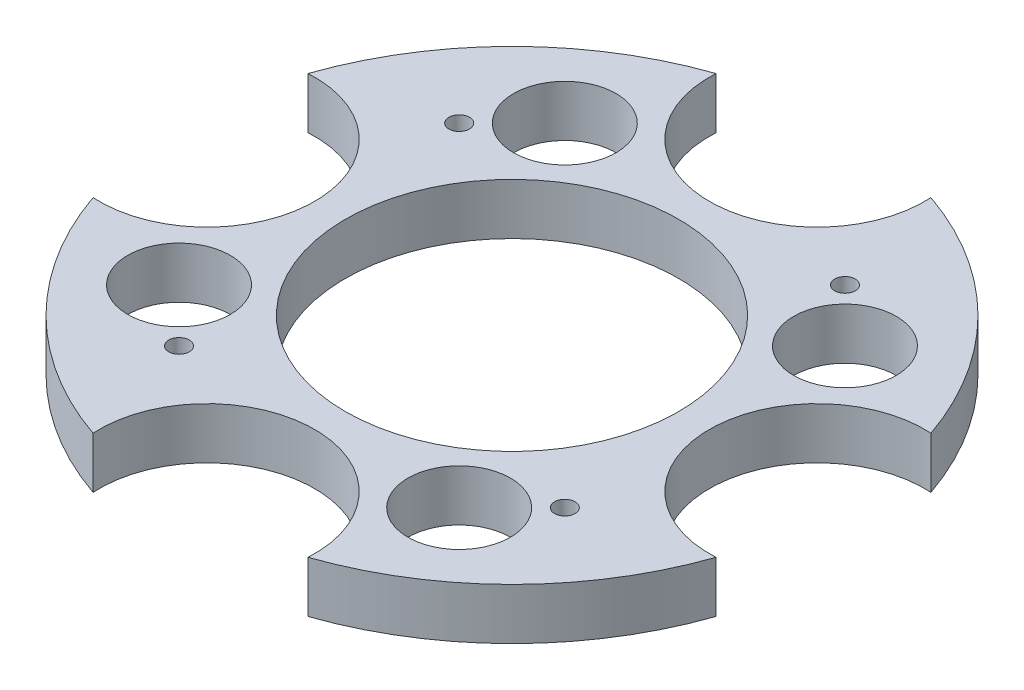
SolidWorks part; units mm, degrees
ref_plane "Front Plane" through (0, 0, 0) normal (0, 0, 1) x (1, 0, 0)
ref_plane "Top Plane" through (0, 0, 0) normal (0, 1, 0) x (1, 0, 0)
ref_plane "Right Plane" through (0, 0, 0) normal (1, 0, 0) x (0, 0, -1)
sketch "Sketch1" plane through (0, 0, 0) normal (0, 1, 0) x (1, 0, 0)
  circle A0 centre (0, 0) radius 32.135
  circle A1 centre (0, 0) radius 16.25
  dimension "D1" = 64.27
  dimension "D2" = 32.5
extrude "Boss-Extrude1" add sketch "Sketch1" along normal mid plane 5
sketch "Sketch2" plane through (0, 2.5, 0) normal (0, 1, 0) x (1, 0, 0)
  line L0 (0, 16.25) -> (0, 19.25) construction
  circle A0 centre (0, 29.75) radius 10.5
  circle A3 centre (0, 0) radius 16.25 construction
  dimension "D1" = 21
  dimension "D2" = 3
extrude "Cut-Extrude1" cut sketch "Sketch2" against normal through all
pattern_circular "CirPattern1" count 4 over 360 about axis through (0, 2.5, 0) along (0, -1, 0) of "Cut-Extrude1" reverse direction yes
sketch "Sketch3" plane through (0, 2.5, 0) normal (0, 1, 0) x (1, 0, 0)
  arc A0 (-10.4812, 30.3777) -> (10.4812, 30.3777) centre (0, 29.75) cw
  arc A1 (-10.4812, 30.3777) -> (10.4812, 30.3777) centre (0, 29.75) ccw construction
  arc A2 (-12.6126, 34.5638) -> (12.6126, 34.5638) centre (0, 29.75) cw
  arc A3 (-12.6126, 34.5638) -> (-19.2914, 25.7002) centre (-31.2979, 41.6953) cw
  arc A4 (-10.4812, 30.3777) -> (-30.3777, 10.4812) centre (0, 0) ccw construction
  arc A5 (-19.2914, 25.7002) -> (-10.4812, 30.3777) centre (0, 0) cw
  arc A6 (10.4812, 30.3777) -> (19.2914, 25.7002) centre (0, 0) cw
  arc A7 (30.3777, 10.4812) -> (10.4812, 30.3777) centre (0, 0) ccw construction
  arc A8 (19.2914, 25.7002) -> (12.6126, 34.5638) centre (31.2979, 41.6953) cw
  point P23 (-18.3629, 26.3716)
  dimension "D1" = 3
  dimension "D2" = 20
extrude "Boss-Extrude2" add sketch "Sketch3" against normal through all
pattern_circular "CirPattern2" count 4 over 360 about axis through (0, 2.5, 0) along (0, -1, 0) of "Boss-Extrude2"
sketch "Sketch4" plane through (0, 2.5, 0) normal (0, 1, 0) x (1, 0, 0)
  line L0 (-16.896, 30.8538) -> (-7.5226, 19.1456) construction
  line L1 (-9.7581, 21.9379) -> (-8.1968, 23.1878) construction
  line L2 (-9.3523, 24.6311) -> (-15.3864, 32.1683) construction
  line L3 (-26.2913, 0.9907) -> (-12.7442, 10.8281) construction
  line L4 (-9.5483, 13.1489) -> (-10.7234, 14.7672) construction
  line L5 (-12.8867, 13.1964) -> (-19.6602, 8.2777) construction
  line L6 (-13.6614, 18.813) -> (13.6614, 18.813) construction
  circle A0 centre (-13.6614, 18.813) radius 5
  circle A1 centre (0, 29.75) radius 10.5 construction
  circle A2 centre (0, 0) radius 16.25 construction
  circle A3 centre (13.6614, 18.813) radius 1
  point P20 (19.7224, 18.813)
  point P21 (0, 18.813)
  dimension "D1" = 10
  dimension "D3" = 2
  dimension "D2" = 2
extrude "Cut-Extrude2" cut sketch "Sketch4" against normal through all
pattern_circular "CirPattern3" count 4 over 360 about axis through (0, 2.5, 0) along (0, -1, 0) of "Cut-Extrude2" reverse direction yes
sketch "Sketch5" plane through (0, 2.5, 0) normal (0, 1, 0) x (1, 0, 0)
  circle A0 centre (0, 0) radius 32.135
  circle A1 centre (0, 0) radius 43.25
  arc A2 (-19.2914, 25.7002) -> (-25.7002, 19.2914) centre (0, 0) ccw construction
  arc A3 (-34.5638, 12.6126) -> (-34.5638, -12.6126) centre (-29.75, 0) ccw construction
extrude "Cut-Extrude3" cut sketch "Sketch5" against normal through all
